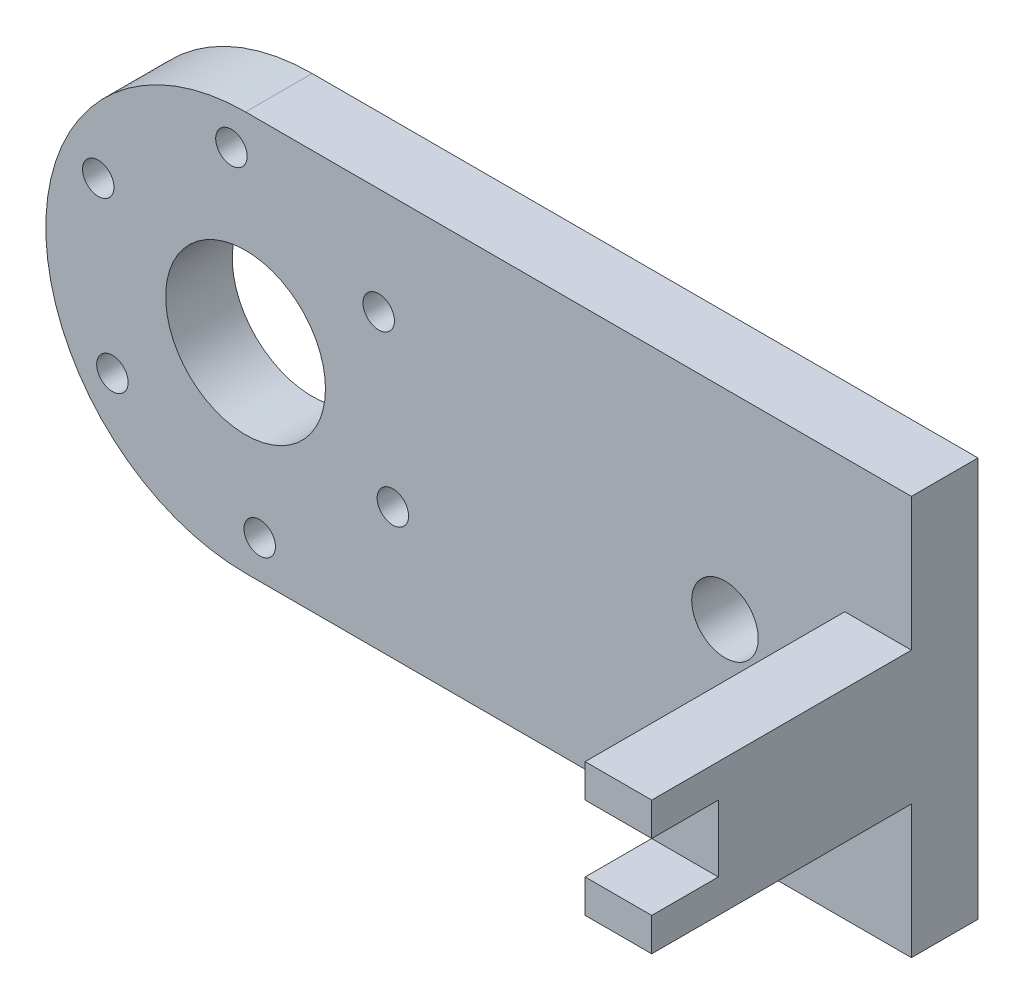
SolidWorks part; units mm, degrees
ref_plane "Front Plane" through (0, 0, 0) normal (0, 0, 1) x (1, 0, 0)
ref_plane "Top Plane" through (0, 0, 0) normal (0, 1, 0) x (1, 0, 0)
ref_plane "Right Plane" through (0, 0, 0) normal (1, 0, 0) x (0, 0, -1)
sketch "Sketch1" plane through (0, 0, 0) normal (0, 0, 1) x (1, 0, 0)
  line L1 (0, 19.05) -> (63.5, 19.05)
  line L2 (0, 19.05) -> (0, -19.05)
  line L3 (0, -19.05) -> (63.5, -19.05)
  line L4 (63.5, 19.05) -> (63.5, -19.05)
  circle A0 centre (0, 0) radius 19.05
  dimension "D1" = 38.1
  dimension "D2" = 63.5
extrude "Boss-Extrude1" add sketch "Sketch1" along normal blind 6.35 contours L2 L1 L4 L3 | A0
sketch "Sketch2" plane through (0, 0, 6.35) normal (0, 0, 1) x (1, 0, 0)
  line L0 (0, 0) -> (0, 15.5) construction
  line L1 (0, 0) -> (-1.3509, 15.441) construction
  line L2 (0, 0) -> (1.3509, -15.441) construction
  circle A0 centre (0, 0) radius 7.62
  circle A1 centre (0, 0) radius 15.5 construction
  circle A2 centre (-1.3509, 15.441) radius 1.5
  circle A3 centre (12.6969, 8.8904) radius 1.5
  circle A4 centre (14.0478, -6.5506) radius 1.5
  circle A5 centre (1.3509, -15.441) radius 1.5
  circle A6 centre (-12.6969, -8.8904) radius 1.5
  circle A7 centre (-14.0478, 6.5506) radius 1.5
  point P20 (0, 0)
  dimension "D1" = 15.24
  dimension "D2" = 31
  dimension "D4" = 3
  dimension "D3" = 5
  dimension "D5" = 6
extrude "Cut-Extrude1" cut sketch "Sketch2" against normal through all
ref_plane "Plane1" through (0, 0, 0) normal (0, 1, 0) x (1, 0, 0)
sketch "Sketch4" plane through (0, 0, 0) normal (0, 1, 0) x (1, 0, 0)
  line L1 (63.5, -6.35) -> (57.15, -6.35)
  line L2 (63.5, -6.35) -> (63.5, -31.115)
  line L3 (63.5, -31.115) -> (57.15, -31.115)
  line L4 (57.15, -6.35) -> (57.15, -31.115)
  dimension "D1" = 6.35
  dimension "D2" = 24.765
extrude "Boss-Extrude2" add sketch "Sketch4" along normal mid plane 12.7
sketch "Sketch5" plane through (63.5, 0, 0) normal (1, 0, 0) x (0, 0, -1)
  line L0 (-31.115, 6.35) -> (-31.115, -6.35) construction
  line L1 (-31.115, 3.175) -> (-24.765, 3.175)
  line L2 (-31.115, 3.175) -> (-31.115, -3.175)
  line L3 (-31.115, -3.175) -> (-24.765, -3.175)
  line L4 (-24.765, 3.175) -> (-24.765, -3.175)
  line L5 (0, 0) -> (-31.115, 0) construction
  line L6 (20.3625, 0) -> (-20.3625, 0) construction
  point P11 (-24.765, 0)
  dimension "D1" = 6.35
  dimension "D2" = 6.35
extrude "Cut-Extrude2" cut sketch "Sketch5" against normal up to next
sketch "Sketch6" plane through (0, 0, 0) normal (0, 0, -1) x (-1, 0, 0)
  line L0 (-63.5, 0) -> (0, 0) construction
  line L1 (-63.5, 19.05) -> (-63.5, -19.05) construction
  circle A0 centre (-45.72, 0) radius 3.175
  dimension "D1" = 6.35
  dimension "D2" = 45.72
extrude "Cut-Extrude3" cut sketch "Sketch6" against normal up to next
